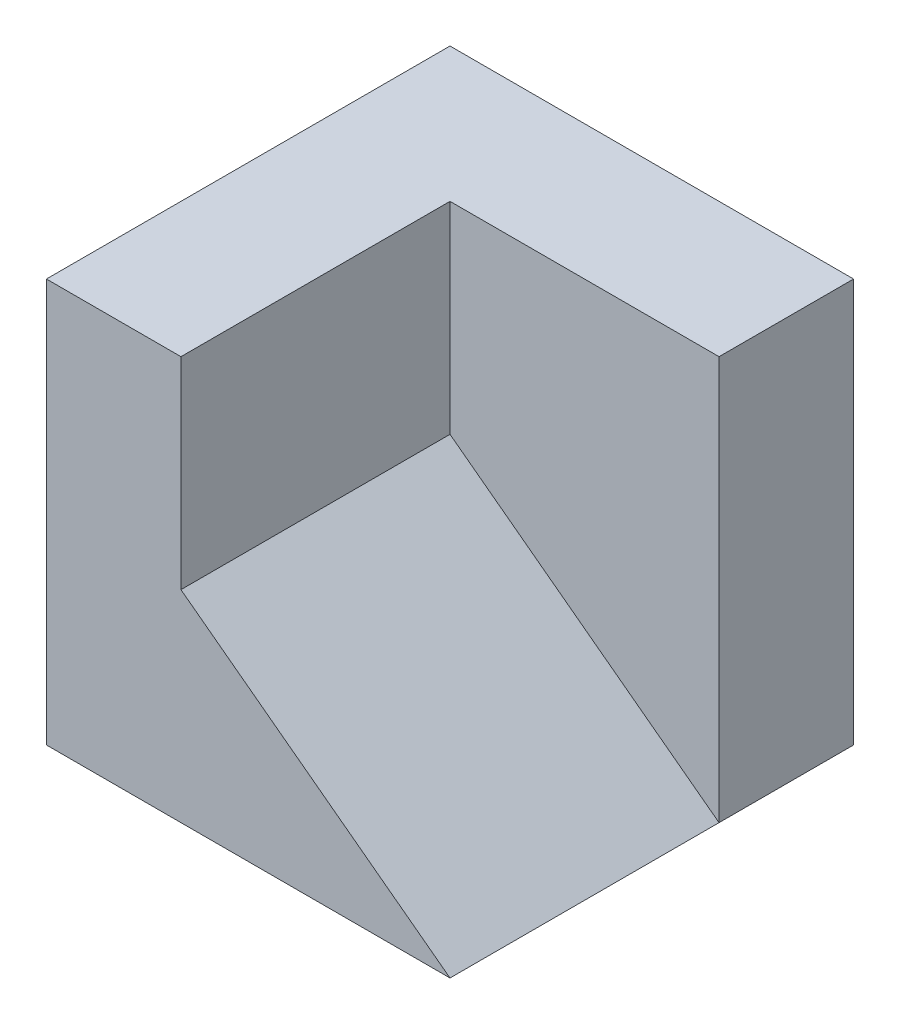
SolidWorks part; units mm, degrees
ref_plane "Alzado" through (0, 0, 0) normal (0, 0, 1) x (1, 0, 0)
ref_plane "Planta" through (0, 0, 0) normal (0, 1, 0) x (1, 0, 0)
ref_plane "Vista lateral" through (0, 0, 0) normal (1, 0, 0) x (0, 0, -1)
sketch "Croquis1" plane through (0, 0, 0) normal (0, 1, 0) x (1, 0, 0)
  line L0 (0, 0) -> (-20, 0)
  line L1 (-20, 0) -> (-20, 60)
  line L2 (-20, 60) -> (40, 60)
  line L3 (40, 60) -> (40, 40)
  line L4 (40, 40) -> (0, 40)
  line L5 (0, 40) -> (0, 0)
  point P3 (0, 44.4848)
  dimension "D1" = 60
  dimension "D2" = 60
  dimension "D3" = 20
  dimension "D4" = 20
extrude "Saliente-Extruir1" add sketch "Croquis1" along normal blind 60 contours L5 L0 L1 L2 L3 L4
sketch "Croquis2" plane through (0, 0, 0) normal (0, 1, 0) x (1, 0, 0)
  line L0 (0, 0) -> (40, 0)
  line L1 (40, 0) -> (40, 40)
  line L2 (40, 40) -> (0, 40)
  line L3 (0, 40) -> (0, 0)
  dimension "D1" = 40
extrude "Saliente-Extruir2" add sketch "Croquis2" along normal blind 30 contours L3 L0 L1 L2
chamfer "Chaflán1" distance 30 distance2 40 1 edges at (40, 30, -20) first distance on face at (40, 30, -33.3333)
